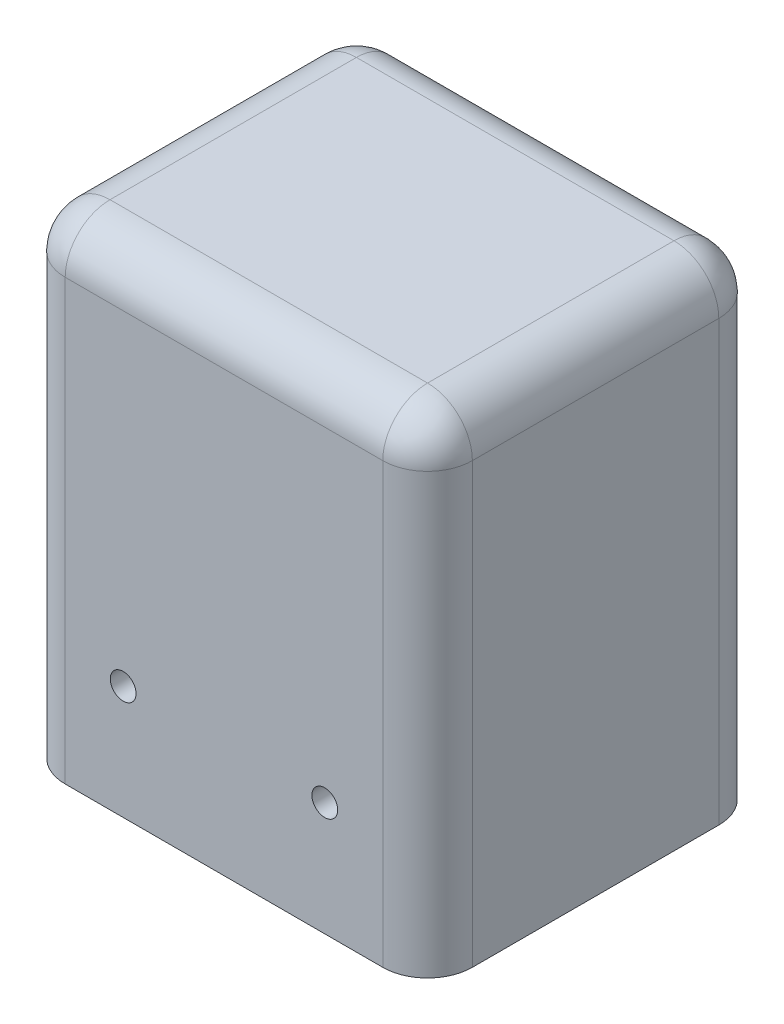
SolidWorks part; units mm, degrees
ref_plane "Front Plane" through (0, 0, 0) normal (0, 0, 1) x (1, 0, 0)
ref_plane "Top Plane" through (0, 0, 0) normal (0, 1, 0) x (1, 0, 0)
ref_plane "Right Plane" through (0, 0, 0) normal (1, 0, 0) x (0, 0, -1)
sketch "Sketch1" plane through (0, 0, 0) normal (0, 1, 0) x (1, 0, 0)
  line L1 (-18.175, 15) -> (18.175, 15)
  line L2 (-18.175, 15) -> (-18.175, -15)
  line L3 (-18.175, -15) -> (18.175, -15)
  line L4 (18.175, 15) -> (18.175, -15)
  line L5 (-18.175, 15) -> (18.175, -15) construction
  line L6 (-18.175, -15) -> (18.175, 15) construction
  line L7 (-15, 11.825) -> (15, 11.825)
  line L8 (-15, 11.825) -> (-15, -11.825)
  line L9 (-15, -11.825) -> (15, -11.825)
  line L10 (15, 11.825) -> (15, -11.825)
  line L11 (-15, 11.825) -> (15, -11.825) construction
  line L12 (-15, -11.825) -> (15, 11.825) construction
  point P0 (0, 0)
  point P6 (0, 0)
  dimension "D1" = 3.175
  dimension "D2" = 3.175
  dimension "D3" = 30
  dimension "D4" = 30
extrude "Boss-Extrude1" add sketch "Sketch1" along normal blind 40
sketch "Sketch2" plane through (0, 40, 0) normal (0, 1, 0) x (1, 0, 0)
  line L1 (-18.175, -15) -> (18.175, -15)
  line L2 (-18.175, -15) -> (-18.175, 15)
  line L3 (-18.175, 15) -> (18.175, 15)
  line L4 (18.175, -15) -> (18.175, 15)
extrude "Boss-Extrude2" add sketch "Sketch2" along normal blind 3.175
fillet "Fillet1" radius 4 8 edges at (-18.175, 43.175, 0) (-18.175, 21.5875, -15) (0, 43.175, -15) (18.175, 21.5875, -15) (18.175, 43.175, 0) (0, 43.175, 15) (18.175, 21.5875, 15) (-18.175, 21.5875, 15)
sketch "Sketch3" plane through (0, 0, 15) normal (0, 0, 1) x (1, 0, 0)
  line L0 (0, 0) -> (0, 39.175) construction
  line L1 (-14.175, 0) -> (14.175, 0) construction
  line L2 (14.175, 39.175) -> (-14.175, 39.175) construction
  circle A0 centre (-9, 10.145) radius 1.15
  circle A1 centre (9, 10.145) radius 1.15
  dimension "D1" = 2.3
  dimension "D2" = 9
  dimension "D3" = 10.145
extrude "Cut-Extrude1" cut sketch "Sketch3" against normal up to surface (3.175 mm away) up to face at (0, 20, 11.825)
